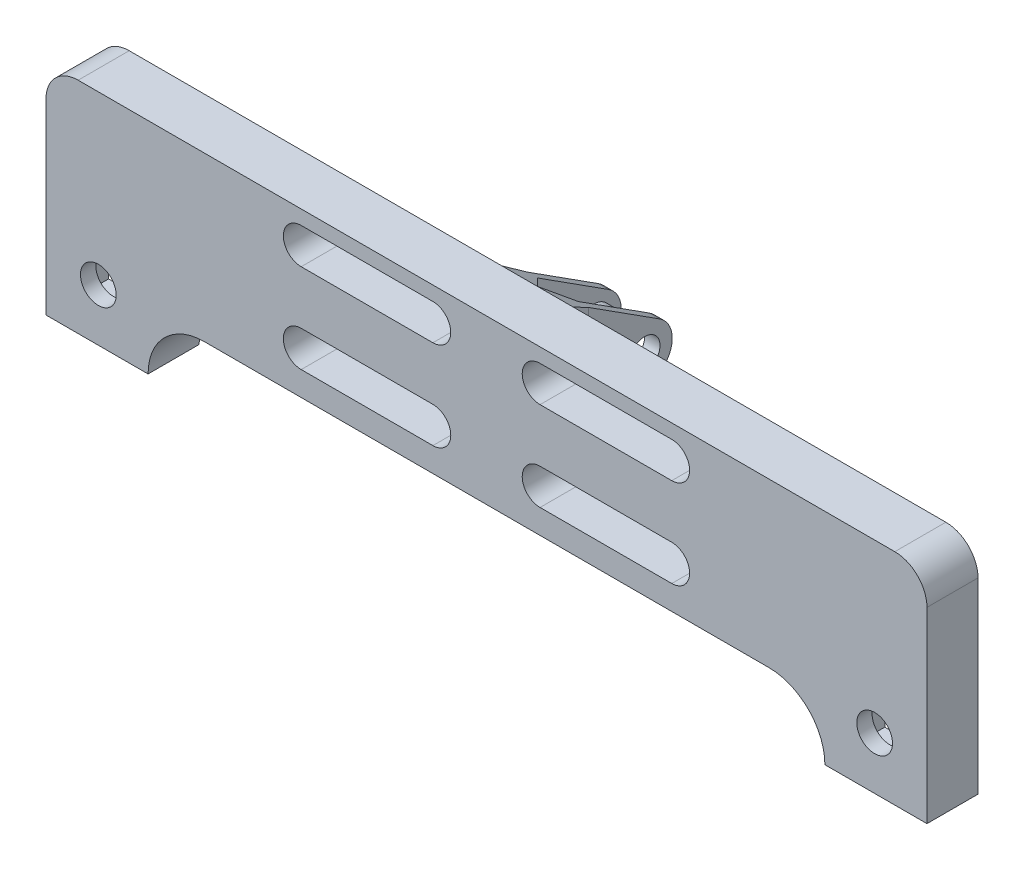
SolidWorks part; units mm, degrees
ref_plane "Front Plane" through (0, 0, 0) normal (0, 0, 1) x (1, 0, 0)
ref_plane "Top Plane" through (0, 0, 0) normal (0, 1, 0) x (1, 0, 0)
ref_plane "Right Plane" through (0, 0, 0) normal (1, 0, 0) x (0, 0, -1)
sketch "Sketch1" plane through (0, 0, 0) normal (0, 0, 1) x (1, 0, 0)
  line L0 (-79.0453, -25.7) -> (80.9547, -25.7) construction
  line L1 (-79.0453, 29.8613) -> (-79.0453, -49.0079) construction
  line L2 (80.9547, 29.8613) -> (80.9547, -49.0079) construction
  line L3 (-85.3453, -25.7) -> (87.2547, -25.7)
  line L4 (87.2547, -25.7) -> (87.2547, 0)
  line L5 (-79.0453, 6.3) -> (80.9547, 6.3)
  line L6 (-85.3453, 0) -> (-85.3453, -25.7)
  line L8 (-83.3453, -11.2) -> (-70.8453, -11.2)
  line L9 (-83.3453, -11.2) -> (-83.3453, -23.7)
  line L10 (-83.3453, -23.7) -> (-70.8453, -23.7)
  line L11 (-70.8453, -11.2) -> (-70.8453, -23.7)
  line L12 (85.2547, -11.2) -> (72.7547, -11.2)
  line L13 (85.2547, -11.2) -> (85.2547, -23.7)
  line L14 (85.2547, -23.7) -> (72.7547, -23.7)
  line L15 (72.7547, -11.2) -> (72.7547, -23.7)
  circle A0 centre (-79.0453, 0) radius 4.3
  circle A1 centre (80.9547, 0) radius 4.3
  arc A2 (-79.0453, 6.3) -> (-85.3453, 0) centre (-79.0453, 0) ccw
  arc A3 (80.9547, 6.3) -> (87.2547, 0) centre (80.9547, 0) cw
  dimension "D2" = 8.6
  dimension "D3" = 8.6
  dimension "D4" = 6.3
  dimension "D5" = 6.3
  dimension "D1" = 160
  dimension "D6" = 32
  dimension "D7" = 2
  dimension "D8" = 2
  dimension "D9" = 12.5
  dimension "D10" = 12.5
  dimension "D11" = 2
  dimension "D12" = 2
  dimension "D13" = 12.5
  dimension "D14" = 12.5
extrude "Boss-Extrude1" add sketch "Sketch1" along normal blind 8
sketch "Sketch2" plane through (0, 0, 8) normal (0, 0, 1) x (1, 0, 0)
  line L0 (-79.0453, 0) -> (80.9547, 0) construction
  line L1 (-35.3453, 6.3) -> (-35.3453, -25.7) construction
  line L2 (80.9547, 6.3) -> (-79.0453, 6.3) construction
  line L3 (-85.3453, -25.7) -> (87.2547, -25.7) construction
  line L4 (-70.8453, -17.45) -> (72.7547, -17.45) construction
  line L5 (-70.8453, -23.7) -> (-70.8453, -11.2) construction
  line L6 (72.7547, -11.2) -> (72.7547, -23.7) construction
  line L7 (37.2547, 6.3) -> (37.2547, -25.7) construction
  line L8 (-85.3453, 0) -> (-85.3453, -25.7) construction
  line L9 (87.2547, -25.7) -> (87.2547, 0) construction
  line L10 (-35.3453, 3.5) -> (37.2547, 3.5)
  line L11 (-35.3453, -3.5) -> (37.2547, -3.5)
  line L12 (-35.3453, -13.95) -> (37.2547, -13.95)
  line L13 (-35.3453, -20.95) -> (34.6432, -20.95)
  line L14 (34.6432, -20.95) -> (37.2547, -20.95)
  arc A0 (-35.3453, 3.5) -> (-35.3453, -3.5) centre (-35.3453, 0) ccw
  arc A1 (37.2547, 3.5) -> (37.2547, -3.5) centre (37.2547, 0) cw
  arc A2 (-35.3453, -13.95) -> (-35.3453, -20.95) centre (-35.3453, -17.45) ccw
  arc A3 (37.2547, -13.95) -> (37.2547, -20.95) centre (37.2547, -17.45) cw
  dimension "D1" = 50
  dimension "D2" = 50
extrude "Cut-Extrude1" cut sketch "Sketch2" against normal blind 8
extrude "Boss-Extrude2" add sketch "Sketch1<2>" along normal blind 10
sketch "Sketch1<2>" plane through (0, 0, 0) normal (0, 0, 1) x (1, 0, 0) same geometry as "Sketch1"
extrude "Cut-Extrude2" cut sketch "Sketch2<2>" against normal through all both and the other way through all
sketch "Sketch2<2>" plane through (0, 0, 8) normal (0, 0, 1) x (1, 0, 0) same geometry as "Sketch2"
sketch "Sketch3" plane through (0, 0, 10) normal (0, 0, 1) x (1, 0, 0)
  line L1 (-83.3453, -11.2) -> (-70.8453, -11.2)
  line L2 (-83.3453, -11.2) -> (-83.3453, -23.7)
  line L3 (-83.3453, -23.7) -> (-70.8453, -23.7)
  line L4 (-70.8453, -11.2) -> (-70.8453, -23.7)
  line L5 (72.7547, -11.2) -> (85.2547, -11.2)
  line L6 (72.7547, -11.2) -> (72.7547, -23.7)
  line L7 (72.7547, -23.7) -> (85.2547, -23.7)
  line L8 (85.2547, -11.2) -> (85.2547, -23.7)
extrude "Boss-Extrude3" add sketch "Sketch3" against normal blind 2
sketch "Sketch4" plane through (0, 0, 10) normal (0, 0, 1) x (1, 0, 0)
  circle A0 centre (-79.0453, 0) radius 4.3
  circle A1 centre (80.9547, 0) radius 4.3
extrude "Boss-Extrude5" add sketch "Sketch4" against normal blind 2
sketch "Sketch5" plane through (0, 0, 10) normal (0, 0, 1) x (1, 0, 0)
  line L0 (0.9547, 3.5) -> (0.9547, -20.95) construction
  line L1 (37.2547, 3.5) -> (-35.3453, 3.5) construction
  line L2 (-35.3453, -20.95) -> (37.2547, -20.95) construction
  line L3 (-38.8453, -17.45) -> (40.7547, -17.45) construction
  line L4 (-38.8453, 0) -> (40.7547, 0) construction
  line L6 (-35.3453, -3.5) -> (37.2547, -3.5) construction
  line L7 (-4.5453, 3.5) -> (6.4547, 3.5)
  line L8 (-4.5453, -3.5) -> (6.4547, -3.5)
  arc A0 (-35.3453, -13.95) -> (-35.3453, -20.95) centre (-35.3453, -17.45) ccw construction
  arc A1 (37.2547, -20.95) -> (37.2547, -13.95) centre (37.2547, -17.45) ccw construction
  arc A2 (-35.3453, 3.5) -> (-35.3453, -3.5) centre (-35.3453, 0) ccw construction
  arc A3 (37.2547, -3.5) -> (37.2547, 3.5) centre (37.2547, 0) ccw construction
  arc A4 (-4.5453, 3.5) -> (-4.5453, -3.5) centre (-4.5453, 0) cw
  arc A5 (6.4547, 3.5) -> (6.4547, -3.5) centre (6.4547, 0) ccw
  point P22 (-4.5453, 0)
  point P23 (6.4547, 0)
  dimension "D1" = 5.5
  dimension "D2" = 5.5
extrude "Boss-Extrude6" add sketch "Sketch5" against normal blind 10
sketch "Sketch6" plane through (0, 0, 10) normal (0, 0, 1) x (1, 0, 0)
  line L0 (0.9547, -13.95) -> (0.9547, -20.95) construction
  line L1 (37.2547, -13.95) -> (-35.3453, -13.95) construction
  line L2 (-35.3453, -20.95) -> (37.2547, -20.95) construction
  line L3 (-38.8453, -17.45) -> (40.7547, -17.45) construction
  line L4 (-4.5453, -13.95) -> (6.4547, -13.95)
  line L5 (-4.5453, -20.95) -> (6.4547, -20.95)
  arc A0 (-35.3453, -13.95) -> (-35.3453, -20.95) centre (-35.3453, -17.45) ccw construction
  arc A1 (37.2547, -20.95) -> (37.2547, -13.95) centre (37.2547, -17.45) ccw construction
  arc A2 (-4.5453, -13.95) -> (-4.5453, -20.95) centre (-4.5453, -17.45) cw
  arc A3 (6.4547, -13.95) -> (6.4547, -20.95) centre (6.4547, -17.45) ccw
  point P14 (6.4547, -17.45)
  point P15 (-4.5453, -17.45)
  dimension "D1" = 5.5
  dimension "D2" = 5.5
extrude "Boss-Extrude7" add sketch "Sketch6" against normal blind 10
sketch "Sketch7" plane through (0, 0, 10) normal (0, 0, 1) x (1, 0, 0)
  line L0 (-85.3453, -25.7) -> (-85.3453, -36.7)
  line L1 (-85.3453, -36.7) -> (-65.3453, -36.7)
  line L2 (87.2547, -25.7) -> (87.2547, -36.7)
  line L3 (87.2547, -36.7) -> (67.2547, -36.7)
  line L4 (-85.3453, -25.7) -> (87.2547, -25.7) construction
  line L5 (-85.3453, -25.7) -> (-54.3453, -25.7)
  line L6 (87.2547, -25.7) -> (56.2547, -25.7)
  arc A0 (-65.3453, -36.7) -> (-54.3453, -25.7) centre (-54.3453, -36.7) cw
  arc A1 (67.2547, -36.7) -> (56.2547, -25.7) centre (56.2547, -36.7) ccw
  point P7 (-54.3453, -36.7)
  point P9 (56.2547, -36.7)
  dimension "D1" = 20
  dimension "D2" = 20
  dimension "D3" = 11
  dimension "D4" = 11
  dimension "D5" = 11
  dimension "D6" = 11
extrude "Boss-Extrude8" add sketch "Sketch7" against normal blind 10
sketch "Sketch8" plane through (0, 0, 0) normal (0, 0, -1) x (-1, 0, 0)
  line L1 (-86.488, -8.1749) -> (-68.3659, -8.1749)
  line L2 (-86.488, -8.1749) -> (-86.488, -30.6799)
  line L3 (-86.488, -30.6799) -> (-68.3659, -30.6799)
  line L4 (-68.3659, -8.1749) -> (-68.3659, -30.6799)
  line L5 (67.3724, -9.1516) -> (84.2875, -9.1516)
  line L6 (67.3724, -9.1516) -> (67.3724, -27.9201)
  line L7 (67.3724, -27.9201) -> (84.2875, -27.9201)
  line L8 (84.2875, -9.1516) -> (84.2875, -27.9201)
extrude "Boss-Extrude9" add sketch "Sketch8" against normal up to surface (10 mm away) up to face at (21.8547, -17.45, 10)
sketch "Sketch12" plane through (0, 0, 0) normal (0, 0, -1) x (-1, 0, 0)
  line L0 (-67.2547, -36.7) -> (-87.2547, -36.7) construction
  line L1 (-85.2547, -34.7) -> (-68.7547, -34.7)
  line L2 (-85.2547, -34.7) -> (-85.2547, -18.2)
  line L3 (-85.2547, -18.2) -> (-68.7547, -18.2)
  line L4 (-68.7547, -34.7) -> (-68.7547, -18.2)
  line L5 (66.8453, -34.7) -> (83.3453, -34.7)
  line L6 (66.8453, -34.7) -> (66.8453, -18.2)
  line L7 (66.8453, -18.2) -> (83.3453, -18.2)
  line L8 (83.3453, -34.7) -> (83.3453, -18.2)
  line L9 (-87.2547, -36.7) -> (-87.2547, 0) construction
  line L10 (85.3453, -36.7) -> (65.3453, -36.7) construction
  line L11 (85.3453, 0) -> (85.3453, -36.7) construction
  dimension "D1" = 16.5
  dimension "D2" = 2
  dimension "D3" = 2
  dimension "D4" = 2
  dimension "D5" = 2
extrude "Cut-Extrude6" cut sketch "Sketch12" against normal blind 7
sketch "Sketch13" plane through (0, 0, 7) normal (0, 0, -1) x (-1, 0, 0)
  line L0 (-85.2547, -18.2) -> (-68.7547, -34.7) construction
  line L1 (83.3453, -18.2) -> (66.8453, -34.7) construction
  circle A0 centre (75.0953, -26.45) radius 3.5
  circle A1 centre (-77.0047, -26.45) radius 3.5
  dimension "D1" = 7
  dimension "D2" = 7
extrude "Cut-Extrude7" cut sketch "Sketch13" against normal blind 7
sketch "Sketch14" plane through (0, 0, 0) normal (0, 0, -1) x (-1, 0, 0)
  line L0 (-0.9547, 6.3) -> (-0.9547, -25.7) construction
  line L1 (-80.9547, 6.3) -> (79.0453, 6.3) construction
  line L2 (54.3453, -25.7) -> (-56.2547, -25.7) construction
  line L3 (-0.9547, -25.7) -> (-0.9547, -9.7) construction
  line L4 (-75.9547, -5.5) -> (-5.9547, -5.5)
  line L5 (4.0453, -5.5) -> (6.7749, -5.5)
  line L6 (74.0453, -5.5) -> (6.7749, -5.5)
  line L7 (4.0453, -11.95) -> (74.0453, -11.95)
  line L8 (-5.9547, -11.95) -> (-75.9547, -11.95)
  arc A0 (-5.9547, -5.5) -> (-5.9547, -11.95) centre (-5.9547, -8.725) cw
  arc A1 (-75.9547, -11.95) -> (-75.9547, -5.5) centre (-75.9547, -8.725) cw
  arc A2 (4.0453, -11.95) -> (4.0453, -5.5) centre (4.0453, -8.725) cw
  arc A3 (74.0453, -5.5) -> (74.0453, -11.95) centre (74.0453, -8.725) cw
  point P6 (-5.9547, -8.725)
  point P8 (4.0453, -8.725)
  dimension "D1" = 5
  dimension "D4" = 70
  dimension "D5" = 70
  dimension "D6" = 70
  dimension "D7" = 5
  dimension "D8" = 5
extrude "Cut-Extrude11" cut sketch "Sketch14" against normal blind 5
sketch "Sketch15" plane through (0, 0, 0) normal (0, 0, -1) x (-1, 0, 0)
  line L0 (-75.9547, -5.5) -> (-5.9547, -5.5)
  line L1 (-5.9547, -5.5) -> (-75.9547, -5.5) construction
  line L2 (-5.9547, -11.95) -> (-75.9547, -11.95)
  line L3 (-75.9547, -11.95) -> (-5.9547, -11.95) construction
  line L4 (4.0453, -5.5) -> (74.0453, -5.5)
  line L5 (74.0453, -11.95) -> (4.0453, -11.95)
  arc A0 (-75.9547, -5.5) -> (-75.9547, -11.95) centre (-75.9547, -8.725) ccw construction
  arc A1 (-5.9547, -5.5) -> (-5.9547, -11.95) centre (-5.9547, -8.725) cw
  arc A2 (-75.9547, -11.95) -> (-75.9547, -5.5) centre (-75.9547, -8.725) cw
  arc A3 (74.0453, -5.5) -> (74.0453, -11.95) centre (74.0453, -8.725) cw
  arc A4 (4.0453, -11.95) -> (4.0453, -5.5) centre (4.0453, -8.725) cw
extrude "Boss-Extrude10" add sketch "Sketch15" against normal blind 8
sketch "Sketch16" plane through (0, 0, 0) normal (0, 0, -1) x (-1, 0, 0)
  line L0 (-0.9547, 6.3) -> (-0.9547, -25.7) construction
  line L1 (-80.9547, 6.3) -> (79.0453, 6.3) construction
  line L2 (54.3453, -25.7) -> (-56.2547, -25.7) construction
  line L3 (4.5453, -3.5) -> (9.5453, -3.5)
  line L4 (35.3453, -3.5) -> (4.5453, -3.5) construction
  line L5 (4.5453, 3.5) -> (35.3453, 3.5) construction
  line L6 (9.5453, 3.5) -> (4.5453, 3.5)
  arc A0 (9.5453, -3.5) -> (9.5453, 3.5) centre (9.5453, 0) cw
  arc A1 (4.5453, 3.5) -> (4.5453, -3.5) centre (4.5453, 0) ccw
  dimension "D1" = 5
extrude "Boss-Extrude11" add sketch "Sketch16" against normal blind 10
ref_plane "Plane1" through (0.9547, 0, 0) normal (-1, 0, 0) x (0, 0, 1)
mirror "Mirror1" about plane through (0.9547, 0, 0) normal (-1, 0, 0) of "Boss-Extrude11"
sketch "Sketch17" plane through (0, 0, 0) normal (0, 0, -1) x (-1, 0, 0)
  line L0 (9.5453, -20.95) -> (4.5453, -20.95)
  line L1 (35.3453, -20.95) -> (4.5453, -20.95) construction
  line L2 (4.5453, -13.95) -> (9.5453, -13.95)
  line L3 (4.5453, -13.95) -> (35.3453, -13.95) construction
  arc A0 (4.5453, -20.95) -> (4.5453, -13.95) centre (4.5453, -17.45) cw
  arc A1 (9.5453, -13.95) -> (9.5453, -20.95) centre (9.5453, -17.45) ccw
  dimension "D1" = 5
extrude "Boss-Extrude12" add sketch "Sketch17" against normal blind 10
mirror "Mirror2" about plane through (0.9547, 0, 0) normal (-1, 0, 0) of "Boss-Extrude12"
sketch "Sketch18" plane through (0, 0, 0) normal (0, 0, -1) x (-1, 0, 0)
  line L0 (-0.9547, 6.3) -> (-0.9547, -25.7) construction
  line L1 (-5.9547, 2.3) -> (-3.9547, 2.3)
  line L2 (-5.9547, 2.3) -> (-5.9547, -17.7)
  line L3 (-5.9547, -17.7) -> (-3.9547, -17.7)
  line L4 (-3.9547, 2.3) -> (-3.9547, -17.7)
  line L5 (2.0453, 2.3) -> (4.0453, 2.3)
  line L6 (2.0453, 2.3) -> (2.0453, -17.7)
  line L7 (2.0453, -17.7) -> (4.0453, -17.7)
  line L8 (4.0453, 2.3) -> (4.0453, -17.7)
  line L9 (-80.9547, 6.3) -> (79.0453, 6.3) construction
  line L10 (54.3453, -25.7) -> (-56.2547, -25.7) construction
  point P14 (-0.9547, -9.7)
  dimension "D1" = 3
  dimension "D2" = 3
  dimension "D3" = 2
  dimension "D4" = 2
  dimension "D5" = 20
  dimension "D6" = 20
  dimension "D7" = 8
  dimension "D8" = 8
extrude "Boss-Extrude13" add sketch "Sketch18" along normal blind 20
sketch "Sketch19" plane through (-4.0453, 0, 0) normal (-1, 0, 0) x (0, 0, 1)
  line L0 (0, 2.3) -> (-20, -4.7)
  line L1 (-20, -17.7) -> (-20, 2.3) construction
  line L2 (-20, -4.7) -> (-20, 2.3)
  line L3 (-20, 2.3) -> (0, 2.3)
  line L4 (0, -17.7) -> (-20, -17.7)
  line L5 (-20, -17.7) -> (-20, -10.7)
  line L6 (-20, -10.7) -> (0, -17.7)
  dimension "D1" = 7
  dimension "D2" = 7
extrude "Cut-Extrude12" cut sketch "Sketch19" against normal blind 20
sketch "Sketch20" plane through (-4.0453, 0, 0) normal (-1, 0, 0) x (0, 0, 1)
  line L0 (-20, -7.7) -> (0, -7.7) construction
  line L1 (-20, -10.7) -> (-20, -4.7) construction
  line L2 (0, -17.7) -> (0, 2.3) construction
  circle A0 centre (-15, -7.7) radius 3.5
  dimension "D1" = 7
  dimension "D2" = 5
extrude "Cut-Extrude13" cut sketch "Sketch20" against normal blind 20
ref_plane "Plane2" through (0, -7.7, 0) normal (0, 1, 0) x (1, 0, 0)
sketch "Sketch21" plane through (0, 0, 0) normal (0, 0, -1) x (-1, 0, 0)
  line L1 (5.7643, -23.0632) -> (-6.8245, -23.0632)
  line L2 (5.7643, -23.0632) -> (5.7643, 4.8098)
  line L3 (5.7643, 4.8098) -> (-6.8245, 4.8098)
  line L4 (-6.8245, -23.0632) -> (-6.8245, 4.8098)
extrude "Cut-Extrude15" cut sketch "Sketch21" along normal blind 28
sketch "Sketch23" plane through (0, 0, 0) normal (0, 0, -1) x (-1, 0, 0)
  line L0 (-0.9547, -25.7) -> (-0.9547, 6.3) construction
  line L1 (54.3453, -25.7) -> (-56.2547, -25.7) construction
  line L2 (-80.9547, 6.3) -> (79.0453, 6.3) construction
  line L4 (5.0453, -25.7) -> (3.0453, -25.7)
  line L5 (5.0453, -25.7) -> (5.0453, 6.3)
  line L6 (5.0453, 6.3) -> (3.0453, 6.3)
  line L7 (3.0453, -25.7) -> (3.0453, 6.3)
  line L8 (-4.9547, -25.7) -> (-6.9547, -25.7)
  line L9 (-4.9547, -25.7) -> (-4.9547, 6.3)
  line L10 (-4.9547, 6.3) -> (-6.9547, 6.3)
  line L11 (-6.9547, -25.7) -> (-6.9547, 6.3)
  dimension "D1" = 4
  dimension "D2" = 4
  dimension "D3" = 2
  dimension "D4" = 2
extrude "Boss-Extrude14" add sketch "Sketch23" along normal blind 25
sketch "Sketch24" plane through (6.9547, 0, 0) normal (1, 0, 0) x (0, 0, -1)
  line L0 (0, -9.7) -> (25, -9.7) construction
  line L1 (0, 6.3) -> (0, -25.7) construction
  line L2 (25, 6.3) -> (25, -25.7) construction
  circle A0 centre (15, -9.7) radius 3
  dimension "D2" = 6
  dimension "D1" = 15
extrude "Cut-Extrude16" cut sketch "Sketch24" against normal blind 25
sketch "Sketch25" plane through (6.9547, 0, 0) normal (1, 0, 0) x (0, 0, -1)
  line L0 (0, -25.7) -> (25, -9.7) construction
  line L1 (25, 6.3) -> (25, -25.7) construction
  line L2 (25, -9.7) -> (0, 6.3) construction
  line L3 (25, 6.3) -> (0, 6.3) construction
  line L4 (0, 6.3) -> (0, -25.7) construction
  line L5 (17.9058, -14.2403) -> (0, -25.7)
  line L6 (0, -25.7) -> (25, -25.7)
  line L7 (25, -25.7) -> (25, -9.7)
  line L8 (25, -9.7) -> (25, 6.3)
  line L9 (25, 6.3) -> (0, 6.3)
  line L10 (0, 6.3) -> (17.9058, -5.1597)
  arc A0 (17.9058, -5.1597) -> (17.9058, -14.2403) centre (15, -9.7) cw
extrude "Cut-Extrude18" cut sketch "Sketch25" against normal blind 25
ref_plane "Plane3" through (6.9547, 6.3, 0) normal (0, -1, 0) x (-1, 0, 0)
sketch "Sketch28" plane through (6.9547, 6.3, 0) normal (0, -1, 0) x (-1, 0, 0)
  line L0 (0, 0) -> (0, 4)
  line L2 (0, 4) -> (-1, 0)
  line L3 (-74, 0) -> (0, 0) construction
  line L4 (2, 0) -> (2, 4)
  line L5 (2, 4) -> (6, 0)
  line L6 (2, 0) -> (10, 0) construction
  line L7 (6, 0) -> (2, 0)
  line L8 (10, 0) -> (10, 4)
  line L9 (10, 4) -> (6, 0)
  line L10 (6, 0) -> (10, 0)
  line L11 (12, 0) -> (13, 0)
  line L12 (12, 0) -> (86, 0) construction
  line L13 (13, 0) -> (12, 4)
  line L14 (12, 4) -> (12, 0)
  line L15 (-1, 0) -> (0, 0)
  dimension "D1" = 1
  dimension "D2" = 4
  dimension "D3" = 4
  dimension "D4" = 1
  dimension "D5" = 4
  dimension "D6" = 4
  dimension "D7" = 4
  dimension "D8" = 4
extrude "Boss-Extrude15" add sketch "Sketch28" along normal up to surface (32 mm away) contours L7 L5 L4 | L9 L10 L8 | L13 L14 L11 | L2 L15 L0 region at (7.288, 6.3, -1.3333) region at (-1.712, 6.3, -1.3333) region at (3.6213, 6.3, -1.3333) region at (-5.3787, 6.3, -1.3333) up to face at (-4.0453, -19.9701, -8.9529)
sketch "Sketch29" plane through (0, 6.3, 0) normal (0, 1, 0) x (1, 0, 0)
  line L0 (-5.0453, 0) -> (-6.0453, 0)
  line L1 (-6.0453, 0) -> (-5.0453, 4)
  line L2 (-5.0453, 4) -> (-5.0453, 0)
  line L3 (-3.0453, 0) -> (-3.0453, 4)
  line L4 (-3.0453, 4) -> (0.9547, 0)
  line L5 (0.9547, 0) -> (-3.0453, 0)
extrude "Cut-Extrude19" cut sketch "Sketch29" against normal up to surface (2.56 mm away) up to face at (-4.0453, 1.6268, -7.3019)
sketch "Sketch30" plane through (0, 6.3, 0) normal (0, 1, 0) x (1, 0, 0)
  line L0 (0.9547, 0) -> (4.9547, 0)
  line L1 (4.9547, 0) -> (4.9547, 4)
  line L2 (4.9547, 4) -> (0.9547, 0)
  line L3 (6.9547, 0) -> (7.9547, 0)
  line L4 (7.9547, 0) -> (6.9547, 4)
  line L5 (6.9547, 4) -> (6.9547, 0)
extrude "Cut-Extrude20" cut sketch "Sketch30" against normal up to surface up to face at (5.9547, 1.6268, -7.3019)
sketch "Sketch31" plane through (0, 0, 7) normal (0, 0, -1) x (-1, 0, 0)
  line L1 (-68.7547, -18.2) -> (-85.2547, -18.2)
  line L2 (-68.7547, -18.2) -> (-68.7547, -34.7)
  line L3 (-68.7547, -34.7) -> (-85.2547, -34.7)
  line L4 (-85.2547, -18.2) -> (-85.2547, -34.7)
  line L5 (-85.0047, -34.45) -> (-69.0047, -34.45)
  line L6 (-85.0047, -34.45) -> (-85.0047, -18.45)
  line L7 (-85.0047, -18.45) -> (-69.0047, -18.45)
  line L8 (-69.0047, -34.45) -> (-69.0047, -18.45)
  dimension "D1" = 16
  dimension "D2" = 16
  dimension "D3" = 0.25
  dimension "D4" = 0.25
extrude "Boss-Extrude16" add sketch "Sketch31" along normal up to surface (7 mm away) up to face at (-74.7453, 0, 0)
ref_plane "Plane4" through (0.9547, 0, 0) normal (1, 0, 0) x (0, 0, -1)
mirror "Mirror3" about plane through (0.9547, 0, 0) normal (1, 0, 0) of "Boss-Extrude16"
sketch "Sketch32" plane through (0, 0, 0) normal (0, 0, -1) x (-1, 0, 0)
  circle A0 centre (-80.9547, 0) radius 4.3
  circle A1 centre (-80.9547, 0) radius 4.05
  dimension "D1" = 8.1
extrude "Boss-Extrude17" add sketch "Sketch32" against normal up to surface (10 mm away) up to face at (24.3547, -17.45, 10)
mirror "Mirror4" about plane through (0.9547, 0, 0) normal (1, 0, 0) of "Boss-Extrude17"
sketch "Sketch33" plane through (-3.0453, 0, 0) normal (1, 0, 0) x (0, 0, -1)
  circle A0 centre (15, -9.7) radius 3
  circle A1 centre (15, -9.7) radius 3.5
  dimension "D1" = 7
extrude "Boss-Extrude18" add sketch "Sketch33" along normal blind 2
sketch "Sketch34" plane through (4.9547, 0, 0) normal (-1, 0, 0) x (0, 0, 1)
  circle A0 centre (-15, -9.7) radius 3
  circle A1 centre (-15, -9.7) radius 3.5
  dimension "D1" = 7
extrude "Boss-Extrude19" add sketch "Sketch34" along normal blind 1
